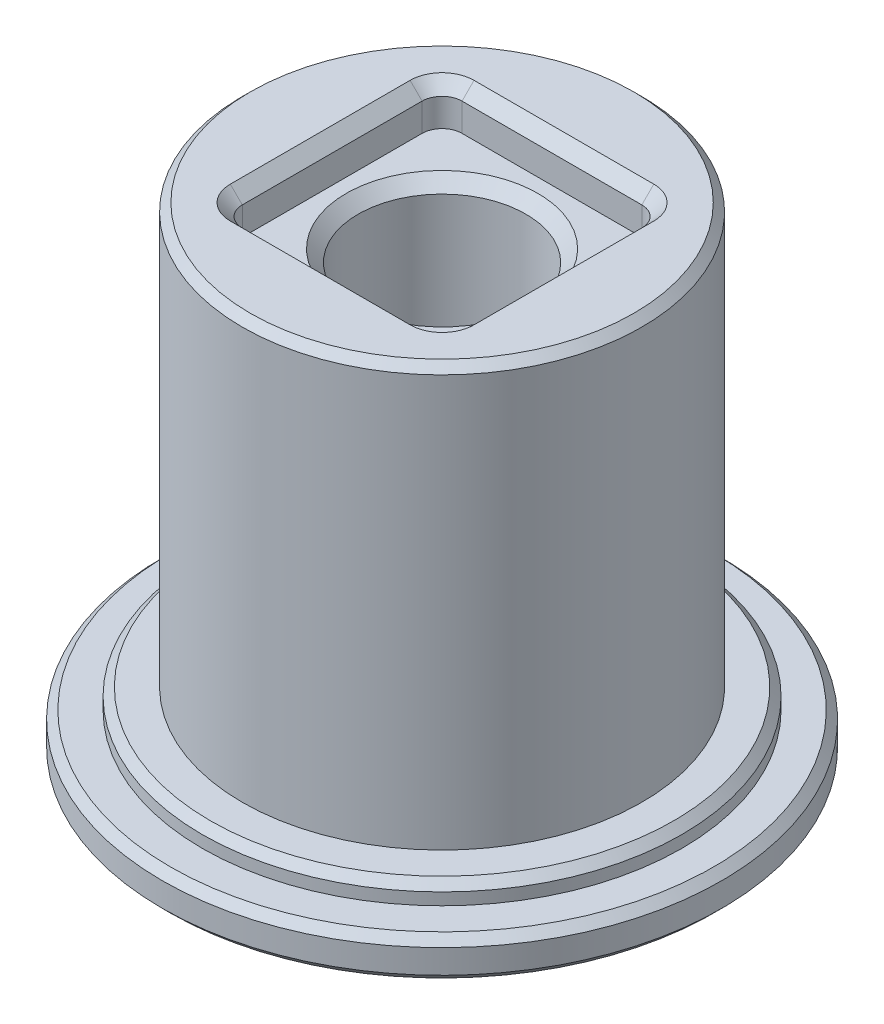
SolidWorks part; units mm, degrees
material "보통 탄소강"
ref_plane "정면" through (0, 0, 0) normal (0, 0, 1) x (1, 0, 0)
ref_plane "윗면" through (0, 0, 0) normal (0, 1, 0) x (1, 0, 0)
ref_plane "우측면" through (0, 0, 0) normal (1, 0, 0) x (0, 0, -1)
sketch "스케치1" plane through (0, 0, 0) normal (0, 1, 0) x (1, 0, 0)
  line L1 (-2.75, -2.75) -> (2.75, -2.75)
  line L2 (-2.75, -2.75) -> (-2.75, 2.75)
  line L3 (-2.75, 2.75) -> (2.75, 2.75)
  line L4 (2.75, -2.75) -> (2.75, 2.75)
  line L5 (-2.75, -2.75) -> (2.75, 2.75) construction
  line L6 (-2.75, 2.75) -> (2.75, -2.75) construction
  circle A0 centre (0, 0) radius 7
  circle A1 centre (0, 0) radius 6
  circle A2 centre (0, 0) radius 5
  circle A3 centre (0, 0) radius 4.25
  circle A5 centre (0, 0) radius 2.1
  dimension "D1" = 14
  dimension "D2" = 12
  dimension "D3" = 10
  dimension "D4" = 8.5
  dimension "D5" = 5.5
  dimension "D6" = 4.2
  dimension "D7" = 5.5
extrude "보스-돌출1" add sketch "스케치1" along normal blind 1 contours A0 A1 region at (-6.802, 0, 0)
extrude "보스-돌출2" add sketch "스케치1<4>" along normal blind 1.5 contours A1 A2 region at (-5.8303, 0, 0)
sketch "스케치1<4>" plane through (0, 0, 0) normal (0, 1, 0) x (1, 0, 0) same geometry as "스케치1"
extrude "보스-돌출3" add sketch "스케치1<5>" along normal blind 12 contours A2 A3 region at (-4.8586, 0, 0)
sketch "스케치1<5>" plane through (0, 0, 0) normal (0, 1, 0) x (1, 0, 0) same geometry as "스케치1"
extrude "보스-돌출4" add sketch "스케치1<6>" along normal blind 7 from offset 5 contours A3 region at (-4.1298, 0, 0)
sketch "스케치1<6>" plane through (0, 0, 0) normal (0, 1, 0) x (1, 0, 0) same geometry as "스케치1"
extrude "보스-돌출5" add sketch "스케치1<7>" along normal blind 6 from offset 5 contours A5 region at (-2.6722, 0, 0)
sketch "스케치1<7>" plane through (0, 0, 0) normal (0, 1, 0) x (1, 0, 0) same geometry as "스케치1"
fillet "필렛1" radius 0.5 4 edges at (2.75, 11.5, 2.75) (-2.75, 11.5, 2.75) (2.75, 11.5, -2.75) (-2.75, 11.5, -2.75)
chamfer "모따기1" distance 0.2 angle 45 4 edges at (0, 12, 5) (0, 1, 7) (0, 0, 7) (0, 1.5, 6)
chamfer "모따기2" distance 0.3 angle 45 1 edges at (0, 0, 4.25)
chamfer "모따기3" distance 0.3 angle 45 9 edges at (0, 11, 2.1) (0, 12, 2.75) (2.75, 12, 0) (-2.75, 12, 0) (0, 12, -2.75) (-2.6036, 12, 2.6036) (2.6036, 12, 2.6036) (-2.6036, 12, -2.6036) (2.6036, 12, -2.6036)
